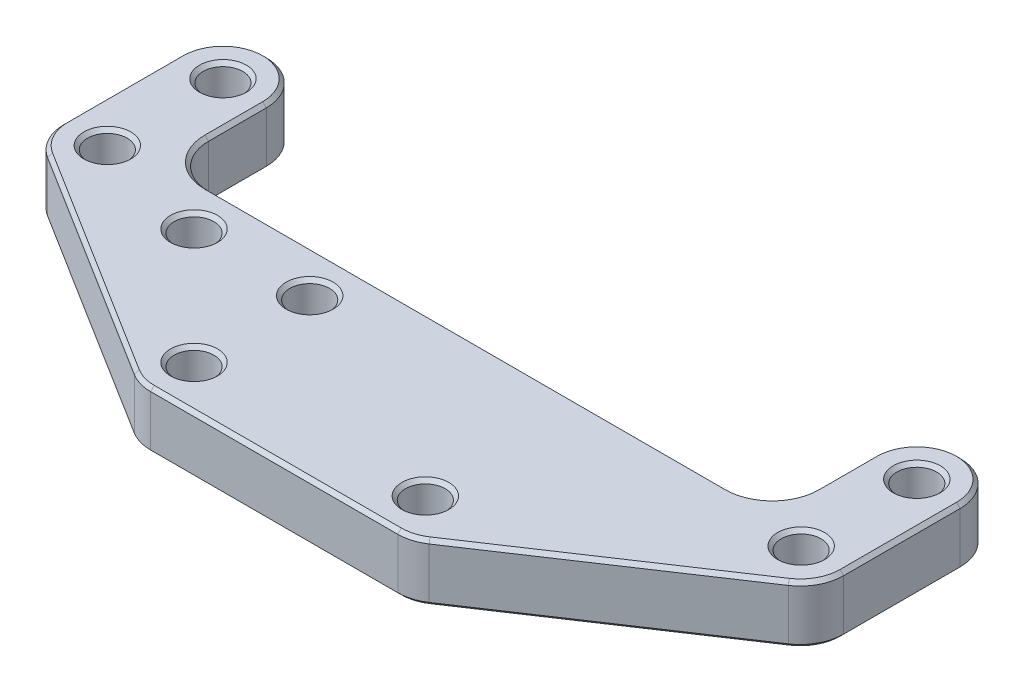
SolidWorks part; units mm, degrees
ref_plane "Front Plane" through (0, 0, 0) normal (0, 0, 1) x (1, 0, 0)
ref_plane "Top Plane" through (0, 0, 0) normal (0, 1, 0) x (1, 0, 0)
ref_plane "Right Plane" through (0, 0, 0) normal (1, 0, 0) x (0, 0, -1)
sketch "Sketch1" plane through (0, 0, 0) normal (0, 1, 0) x (1, 0, 0)
  line L0 (-33.3375, 7.9375) -> (-33.3375, 23.8125)
  line L2 (-42.8625, 23.8125) -> (-42.8625, 3.7104)
  line L4 (42.8625, 23.8125) -> (42.8625, 3.7104)
  line L5 (-33.3375, 7.9375) -> (33.3375, 7.9375)
  line L6 (33.3375, 7.9375) -> (33.3375, 23.8125)
  line L7 (-33.3375, 23.8125) -> (-42.8625, 23.8125)
  line L8 (33.3375, 23.8125) -> (42.8625, 23.8125)
  line L9 (-42.8625, 3.7104) -> (-14.0659, -14.2875)
  line L10 (-14.0659, -14.2875) -> (15.8762, -14.2875)
  line L11 (15.8762, -14.2875) -> (42.8625, 3.7104)
  line L12 (-14.0659, -14.2875) -> (-12.7, -9.525) construction
  line L13 (12.7, -9.525) -> (15.8762, -14.2875) construction
  line L14 (-38.1, 6.35) -> (-42.8625, 3.7104) construction
  circle A0 centre (-38.1, 6.35) radius 2.1828
  circle A1 centre (-38.1, 19.05) radius 2.1828
  circle A2 centre (38.1, 19.05) radius 2.1828
  circle A3 centre (38.1, 6.35) radius 2.1828
  circle A4 centre (-25.4, 3.175) radius 2.1828
  circle A5 centre (-12.7, 3.175) radius 2.1828
  circle A6 centre (-12.7, -9.525) radius 2.1828
  circle A7 centre (12.7, -9.525) radius 2.1828
  point P0 (0, 0)
  point P24 (-44.45, 3.175)
  point P28 (-15.3574, -15.875)
  point P30 (0, 0)
  point P31 (44.45, 3.175)
  point P32 (0, 0)
  point P33 (0, 0)
  point P34 (0, 0)
  point P35 (0, 0)
  point P36 (0, 0)
  point P37 (0, 0)
  dimension "D5" = 4.3656
  dimension "D6" = 4.3656
  dimension "D9" = 4.3656
  dimension "D10" = 4.3656
  dimension "D12" = 4.3656
  dimension "D15" = 4.3656
  dimension "D22" = 4.3656
  dimension "D23" = 4.3656
  dimension "D2" = 6.35
  dimension "D3" = 12.7
  dimension "D4" = 4.7625
  dimension "D7" = 12.7
  dimension "D8" = 4.7625
  dimension "D11" = 3.175
  dimension "D13" = 12.7
  dimension "D14" = 12.7
  dimension "D16" = 76.2
  dimension "D17" = 4.7625
  dimension "D18" = 4.7625
  dimension "D19" = 4.7625
  dimension "D20" = 12.7
  dimension "D21" = 12.7
  dimension "D24" = 4.7625
  dimension "D25" = 9.525
extrude "Boss-Extrude1" add sketch "Sketch1" along normal mid plane 6.35
fillet "Fillet1" radius 4.7625 10 edges at (42.8625, 0, -3.7104) (15.8762, 0, 14.2875) (-14.0659, 0, 14.2875) (-42.8625, 0, -3.7104) (-33.3375, 0, -23.8125) (-42.8625, 0, -23.8125) (42.8625, 0, -23.8125) (33.3375, 0, -23.8125) (33.3375, 0, -7.9375) (-33.3375, 0, -7.9375)
chamfer "Chamfer1" distance 0.3969 angle 45 52 edges at (-12.7, -3.175, 11.7078) (-25.4, -3.175, -0.9922) (38.1, -3.175, -4.1672) (-38.1, -3.175, -16.8672) (41.4676, -3.175, -22.4176) (34.7324, -3.175, -22.4176) (33.3375, -3.175, -15.875) (31.9426, -3.175, -9.3324) (0, -3.175, -7.9375) (-31.9426, -3.175, -9.3324) (-33.3375, -3.175, -15.875) (-34.7324, -3.175, -22.4176) (-41.4676, -3.175, -22.4176) (-42.8625, -3.175, -12.7) (-42.2655, -3.175, -4.0413) (-27.9241, -3.175, 5.6261) (-14.0129, -3.175, 14.1029) (0.8669, -3.175, 14.2875) (15.8143, -3.175, 14.083) (28.9094, -3.175, 5.5953) (42.2992, -3.175, -4.0118) (42.8625, -3.175, -12.6543) (-38.1, -3.175, -4.1672) (38.1, -3.175, -16.8672) (-12.7, -3.175, -0.9922) (12.7, -3.175, 11.7078) (-12.7, 3.175, 11.7078) (12.7, 3.175, 11.7078) (-25.4, 3.175, -0.9922) (-12.7, 3.175, -0.9922) (38.1, 3.175, -4.1672) (38.1, 3.175, -16.8672) (-38.1, 3.175, -16.8672) (-38.1, 3.175, -4.1672) (15.8143, 3.175, 14.083) (0.8669, 3.175, 14.2875) (-14.0129, 3.175, 14.1029) (-27.9241, 3.175, 5.6261) (-42.2655, 3.175, -4.0413) (-42.8625, 3.175, -12.7) (-41.4676, 3.175, -22.4176) (-34.7324, 3.175, -22.4176) (-33.3375, 3.175, -15.875) (-31.9426, 3.175, -9.3324) (0, 3.175, -7.9375) (31.9426, 3.175, -9.3324) (33.3375, 3.175, -15.875) (34.7324, 3.175, -22.4176) (41.4676, 3.175, -22.4176) (42.8625, 3.175, -12.6543) (42.2992, 3.175, -4.0118) (28.9094, 3.175, 5.5953)
